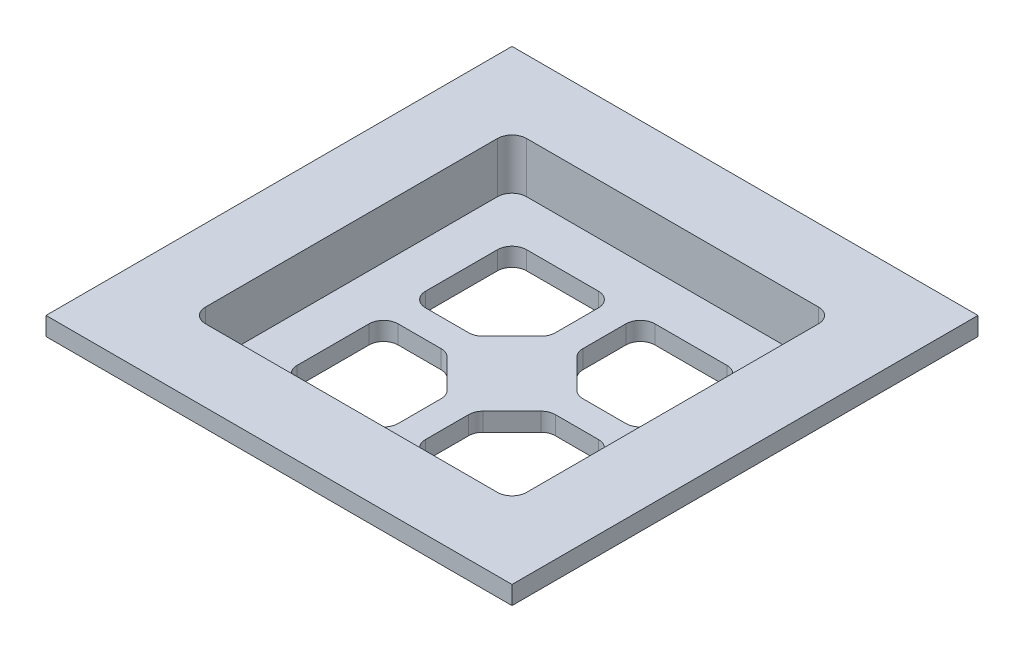
SolidWorks part; units mm, degrees
ref_plane "Front Plane" through (0, 0, 0) normal (0, 0, 1) x (1, 0, 0)
ref_plane "Top Plane" through (0, 0, 0) normal (0, 1, 0) x (1, 0, 0)
ref_plane "Right Plane" through (0, 0, 0) normal (1, 0, 0) x (0, 0, -1)
sketch "Sketch3" plane through (0, 0, 0) normal (0, 1, 0) x (1, 0, 0)
  line L1 (0, 0) -> (47.625, 0) construction
  line L3 (0, 47.625) -> (47.625, 47.625) construction
  line L8 (0, 47.625) -> (0, 0) construction
  line L9 (47.625, 47.625) -> (47.625, 0) construction
  line L14 (0.254, 0.254) -> (47.371, 0.254)
  line L15 (47.371, 47.371) -> (47.371, 0.254)
  line L16 (0.254, 47.371) -> (47.371, 47.371)
  line L17 (0.254, 47.371) -> (0.254, 0.254)
  point P9 (0, 47.625)
  point P12 (0, 0)
  dimension "D2" = 0.254
  dimension "D1" = 47.625
extrude "Boss-Extrude1" add sketch "Sketch3" along normal blind 5.5008
sketch "Sketch6" plane through (0, 5.5008, 0) normal (0, 1, 0) x (1, 0, 0)
  line L7 (22.3125, 36.3125) -> (22.3125, 25.3125)
  line L17 (25.3125, 36.3125) -> (25.3125, 25.3125)
  line L18 (25.3125, 25.3125) -> (36.3125, 25.3125)
  line L20 (25.3125, 22.3125) -> (36.3125, 22.3125)
  line L23 (22.3125, 22.3125) -> (22.3125, 11.3125)
  line L25 (25.3125, 22.3125) -> (25.3125, 11.3125)
  line L26 (11.3125, 25.3125) -> (22.3125, 25.3125)
  line L28 (36.3125, 11.3125) -> (36.3125, 22.3125)
  line L29 (11.3125, 11.3125) -> (22.3125, 11.3125)
  line L30 (11.3125, 36.3125) -> (11.3125, 25.3125)
  line L31 (36.3125, 36.3125) -> (25.3125, 36.3125)
  line L32 (11.3125, 22.3125) -> (22.3125, 22.3125)
  line L35 (11.3125, 22.3125) -> (11.3125, 11.3125)
  line L37 (25.3125, 11.3125) -> (36.3125, 11.3125)
  line L39 (36.3125, 25.3125) -> (36.3125, 36.3125)
  line L40 (22.3125, 36.3125) -> (11.3125, 36.3125)
  line L42 (23.8125, 47.371) -> (23.8125, 0.254) construction
  line L43 (47.371, 47.371) -> (0.254, 47.371) construction
  line L44 (0.254, 0.254) -> (47.371, 0.254) construction
  line L45 (0.254, 23.8125) -> (47.371, 23.8125) construction
  line L46 (0.254, 47.371) -> (0.254, 0.254) construction
  line L47 (47.371, 0.254) -> (47.371, 47.371) construction
  dimension "D2" = 11
  dimension "D7" = 3
  dimension "D8" = 1.5
  dimension "D9" = 1.5
  dimension "D10" = 1.5
  dimension "D11" = 1.5
extrude "Cut-Extrude2" cut sketch "Sketch6" against normal up to next
sketch "Sketch7" plane through (0, 5.5008, 0) normal (0, 1, 0) x (1, 0, 0)
  line L0 (23.8125, 41.3125) -> (23.8125, 47.371) construction
  line L1 (6.3125, 41.3125) -> (41.3125, 41.3125)
  line L2 (6.3125, 41.3125) -> (6.3125, 6.3125)
  line L3 (6.3125, 6.3125) -> (41.3125, 6.3125)
  line L4 (41.3125, 41.3125) -> (41.3125, 6.3125)
  line L5 (47.371, 47.371) -> (0.254, 47.371) construction
  line L6 (6.3125, 23.8125) -> (0.254, 23.8125) construction
  line L7 (0.254, 47.371) -> (0.254, 0.254) construction
  line L9 (-1.5875, 49.2125) -> (49.2125, 49.2125)
  line L10 (-1.5875, 49.2125) -> (-1.5875, -1.5875)
  line L11 (-1.5875, -1.5875) -> (49.2125, -1.5875)
  line L12 (49.2125, 49.2125) -> (49.2125, -1.5875)
  dimension "D1" = 35
  dimension "D2" = 7.9
  dimension "D3" = 7.9
  dimension "D4" = 50.8
extrude "Boss-Extrude2" add sketch "Sketch7" along normal blind 2
sketch "Sketch12" plane through (0, 5.5008, 0) normal (0, 1, 0) x (1, 0, 0)
  line L4 (41.3125, 41.3125) -> (6.3125, 41.3125)
  line L5 (6.3125, 41.3125) -> (6.3125, 6.3125)
  line L6 (6.3125, 6.3125) -> (41.3125, 6.3125)
  line L7 (41.3125, 6.3125) -> (41.3125, 41.3125)
  line L8 (41.3125, 41.3125) -> (6.3125, 41.3125)
  line L9 (6.3125, 41.3125) -> (6.3125, 6.3125)
  line L10 (6.3125, 6.3125) -> (41.3125, 6.3125)
  line L11 (41.3125, 6.3125) -> (41.3125, 41.3125)
  dimension "D1" = 0
extrude "Cut-Extrude3" cut sketch "Sketch12" against normal blind 3.5
sketch "Sketch11" plane through (0, 2.0008, 0) normal (0, 1, 0) x (1, 0, 0)
  line L0 (23.8125, 18.2414) -> (23.8125, 6.3125) construction
  line L1 (22.3125, 29.3836) -> (25.3125, 29.3836)
  line L2 (18.2414, 25.3125) -> (18.2414, 22.3125)
  line L3 (22.3125, 18.2414) -> (25.3125, 18.2414)
  line L4 (29.3836, 25.3125) -> (29.3836, 22.3125)
  line L5 (6.3125, 6.3125) -> (41.3125, 6.3125) construction
  line L6 (29.3836, 23.8125) -> (41.3125, 23.8125) construction
  line L8 (18.2414, 25.3125) -> (22.3125, 29.3836)
  line L10 (25.3125, 29.3836) -> (29.3836, 25.3125)
  line L12 (29.3836, 22.3125) -> (25.3125, 18.2414)
  line L13 (22.3125, 18.2414) -> (18.2414, 22.3125)
  line L20 (41.3125, 6.3125) -> (41.3125, 41.3125) construction
  line L21 (25.3125, 25.3125) -> (25.3125, 36.3125) construction
  line L22 (22.3125, 36.3125) -> (22.3125, 25.3125) construction
  line L23 (36.3125, 25.3125) -> (25.3125, 25.3125) construction
  line L24 (25.3125, 22.3125) -> (36.3125, 22.3125) construction
  line L25 (25.3125, 11.3125) -> (25.3125, 22.3125) construction
  line L26 (22.3125, 22.3125) -> (22.3125, 11.3125) construction
  line L27 (11.3125, 22.3125) -> (22.3125, 22.3125) construction
  line L28 (22.3125, 25.3125) -> (11.3125, 25.3125) construction
  dimension "D1" = 10
  dimension "D2" = 135
extrude "Boss-Extrude4" add sketch "Sketch11" against normal up to surface (2.0008 mm away) up to face at (30.8125, 0, -16.8125)
fillet "Fillet3" radius 1.5875 28 edges at (25.3125, 1.0004, -11.3125) (11.3125, 1.0004, -11.3125) (22.3125, 1.0004, -11.3125) (36.3125, 1.0004, -11.3125) (36.3125, 1.0004, -22.3125) (11.3125, 1.0004, -22.3125) (36.3125, 1.0004, -36.3125) (36.3125, 1.0004, -25.3125) (25.3125, 1.0004, -36.3125) (22.3125, 1.0004, -36.3125) (11.3125, 1.0004, -25.3125) (11.3125, 1.0004, -36.3125) (41.3125, 4.7508, -41.3125) (41.3125, 4.7508, -6.3125) (6.3125, 4.7508, -6.3125) (6.3125, 4.7508, -41.3125) (29.3836, 1.0004, -22.3125) (25.3125, 1.0004, -18.2414) (29.3836, 1.0004, -25.3125) (25.3125, 1.0004, -29.3836) (22.3125, 1.0004, -29.3836) (18.2414, 1.0004, -25.3125) (18.2414, 1.0004, -22.3125) (22.3125, 1.0004, -18.2414) (0.254, 2.7504, -47.371) (47.371, 2.7504, -47.371) (47.371, 2.7504, -0.254) (0.254, 2.7504, -0.254)
sketch "Sketch13" plane through (0, 0, 0) normal (0, -1, 0) x (1, 0, 0)
  line L0 (4.018, -5.6055) -> (4.018, -42.0195)
  line L1 (5.6055, -43.607) -> (42.0195, -43.607)
  line L2 (43.607, -42.0195) -> (43.607, -5.6055)
  line L3 (42.0195, -4.018) -> (5.6055, -4.018)
  line L4 (0.254, -1.8415) -> (0.254, -45.7835)
  line L5 (1.8415, -47.371) -> (45.7835, -47.371)
  line L6 (47.371, -45.7835) -> (47.371, -1.8415)
  line L7 (45.7835, -0.254) -> (1.8415, -0.254)
  line L8 (0.254, -1.8415) -> (0.254, -45.7835)
  line L9 (1.8415, -47.371) -> (45.7835, -47.371)
  line L10 (47.371, -45.7835) -> (47.371, -1.8415)
  line L11 (45.7835, -0.254) -> (1.8415, -0.254)
  line L12 (4.018, -4.018) -> (4.018, -43.607) construction
  line L13 (43.607, -4.018) -> (4.018, -4.018) construction
  line L14 (43.607, -43.607) -> (43.607, -4.018) construction
  line L15 (4.018, -43.607) -> (43.607, -43.607) construction
  arc A4 (0.254, -45.7835) -> (1.8415, -47.371) centre (1.8415, -45.7835) ccw
  arc A5 (45.7835, -47.371) -> (47.371, -45.7835) centre (45.7835, -45.7835) ccw
  arc A6 (47.371, -1.8415) -> (45.7835, -0.254) centre (45.7835, -1.8415) ccw
  arc A7 (1.8415, -0.254) -> (0.254, -1.8415) centre (1.8415, -1.8415) ccw
  arc A8 (0.254, -45.7835) -> (1.8415, -47.371) centre (1.8415, -45.7835) ccw
  arc A9 (45.7835, -47.371) -> (47.371, -45.7835) centre (45.7835, -45.7835) ccw
  arc A10 (47.371, -1.8415) -> (45.7835, -0.254) centre (45.7835, -1.8415) ccw
  arc A11 (1.8415, -0.254) -> (0.254, -1.8415) centre (1.8415, -1.8415) ccw
  arc A12 (43.607, -4.018) -> (43.607, -4.018) centre (43.607, -4.018) ccw construction
  arc A13 (4.018, -4.018) -> (4.018, -4.018) centre (4.018, -4.018) ccw construction
  arc A14 (4.018, -43.607) -> (4.018, -43.607) centre (4.018, -43.607) ccw construction
  arc A15 (43.607, -43.607) -> (43.607, -43.607) centre (43.607, -43.607) ccw construction
  arc A16 (4.018, -5.6055) -> (5.6055, -4.018) centre (5.6055, -5.6055) cw
  arc A17 (43.607, -5.6055) -> (42.0195, -4.018) centre (42.0195, -5.6055) ccw
  arc A18 (42.0195, -43.607) -> (43.607, -42.0195) centre (42.0195, -42.0195) ccw
  arc A19 (5.6055, -43.607) -> (4.018, -42.0195) centre (5.6055, -42.0195) cw
  dimension "D3" = 1.5875
  dimension "D4" = 1.5875
  dimension "D5" = 1.5875
  dimension "D6" = 1.5875
  dimension "D1" = 0
  dimension "D2" = 3.764
extrude "Cut-Extrude5" cut sketch "Sketch13" against normal up to surface (5.5008 mm away) up to face at (23.8125, 5.5008, -23.8125)
